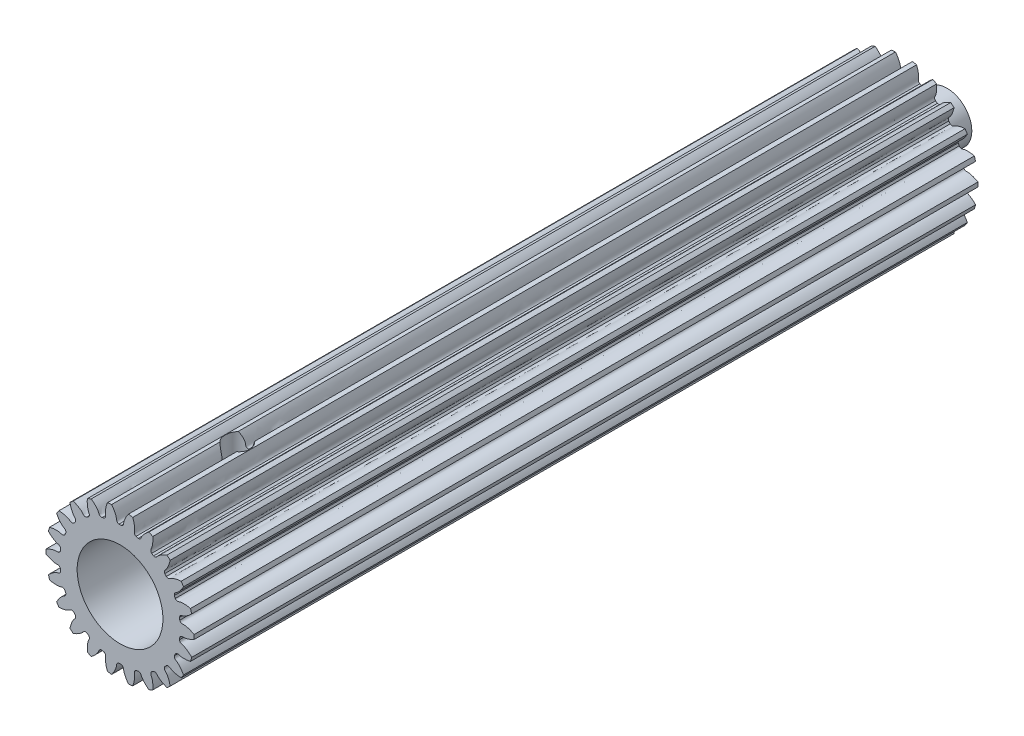
SolidWorks part; units mm, degrees
ref_plane "前视基准面" through (0, 0, 0) normal (0, 0, 1) x (1, 0, 0)
ref_plane "上视基准面" through (0, 0, 0) normal (0, 1, 0) x (1, 0, 0)
ref_plane "右视基准面" through (0, 0, 0) normal (1, 0, 0) x (0, 0, -1)
sketch "草图1" plane through (0, 0, 0) normal (0, 0, 1) x (1, 0, 0)
  circle A0 centre (0, 0) radius 12
extrude "凸台-拉伸1" add sketch "草图1" along normal blind 30
ref_axis "基准轴1" through (0, 0, -1.5) along (0, 0, 1)
sketch "草图2" plane through (0, 0, 0) normal (0, 0, 1) x (1, 0, 0)
  line L0 (0, 0) -> (0, 12) construction
  circle A0 centre (0, 0) radius 12 construction
  arc A1 (0.1857, 9.7482) -> (-0.1857, 9.7482) centre (0, 0) ccw
  arc A2 (3.0856, 13.5599) -> (-3.0856, 13.5599) centre (0, 0) ccw
  spline S0 degree 3 poles (0.1857, 9.7482) (0.5882, 9.8762) (0.5483, 10.1518) (0.5996, 10.4216) (0.606, 10.4519) (0.6139, 10.4862) (0.6235, 10.5243) (0.6349, 10.5661) (0.6484, 10.6117) (0.664, 10.661) (0.6819, 10.7139) (0.7023, 10.7703) (0.7253, 10.8301) (0.7511, 10.8933) (0.7797, 10.9597) (0.8114, 11.0293) (0.8462, 11.1021) (0.8843, 11.1778) (0.9259, 11.2563) (0.9711, 11.3377) (1.0199, 11.4217) (1.0726, 11.5082) (1.1292, 11.5972) (1.1899, 11.6884) (1.2547, 11.7818) (1.3238, 11.8773) (1.3973, 11.9746) (1.4753, 12.0737) (1.5579, 12.1744) (1.6452, 12.2766) (1.7372, 12.3802) (1.8341, 12.4849) (1.9359, 12.5906) (2.0428, 12.6972) (2.1547, 12.8044) (2.2718, 12.9123) (2.3942, 13.0205) (2.5218, 13.1289) (2.6548, 13.2373) (2.8415, 13.3834) (2.9864, 13.49) (3.0856, 13.5599) knots 0 0 0 0 0.157021 0.162531 0.168888 0.176093 0.184146 0.193046 0.202794 0.213389 0.224833 0.237123 0.250262 0.264248 0.279082 0.294763 0.311292 0.328669 0.346893 0.365965 0.385884 0.406652 0.428266 0.450729 0.474039 0.498197 0.523202 0.549055 0.575756 0.603304 0.6317 0.660944 0.691035 0.721974 0.75376 0.786395 0.819876 0.854206 0.889383 0.925408 1 1 1 1
  spline S1 degree 3 poles (-0.1857, 9.7482) (-0.5882, 9.8762) (-0.5483, 10.1518) (-0.5996, 10.4216) (-0.606, 10.4519) (-0.6139, 10.4862) (-0.6235, 10.5243) (-0.6349, 10.5661) (-0.6484, 10.6117) (-0.664, 10.661) (-0.6819, 10.7139) (-0.7023, 10.7703) (-0.7253, 10.8301) (-0.7511, 10.8933) (-0.7797, 10.9597) (-0.8114, 11.0293) (-0.8462, 11.1021) (-0.8843, 11.1778) (-0.9259, 11.2563) (-0.9711, 11.3377) (-1.0199, 11.4217) (-1.0726, 11.5082) (-1.1292, 11.5972) (-1.1899, 11.6884) (-1.2547, 11.7818) (-1.3238, 11.8773) (-1.3973, 11.9746) (-1.4753, 12.0737) (-1.5579, 12.1744) (-1.6452, 12.2766) (-1.7372, 12.3802) (-1.8341, 12.4849) (-1.9359, 12.5906) (-2.0428, 12.6972) (-2.1547, 12.8044) (-2.2718, 12.9123) (-2.3942, 13.0205) (-2.5218, 13.1289) (-2.6548, 13.2373) (-2.8415, 13.3834) (-2.9864, 13.49) (-3.0856, 13.5599) knots 0 0 0 0 0.157021 0.162531 0.168888 0.176093 0.184146 0.193046 0.202794 0.213389 0.224833 0.237123 0.250262 0.264248 0.279082 0.294763 0.311292 0.328669 0.346893 0.365965 0.385884 0.406652 0.428266 0.450729 0.474039 0.498197 0.523202 0.549055 0.575756 0.603304 0.6317 0.660944 0.691035 0.721974 0.75376 0.786395 0.819876 0.854206 0.889383 0.925408 1 1 1 1
extrude "切除-拉伸1" cut sketch "草图2" along normal through all
pattern_circular "阵列(圆周)1" count 22 every 16.364 about axis through (0, 0, -1.5) along (0, 0, 1) of "切除-拉伸1"
sketch "草图3" plane through (0, 0, 0) normal (0, 0, 1) x (1, 0, 0)
  circle A0 centre (0, 0) radius 11 construction
  dimension "Dn" = 22
sketch "草图4" plane through (0, 0, 0) normal (0, 0, -1) x (-1, 0, 0)
  arc A45 (2.9245, 9.3011) -> (2.5682, 9.4057) centre (0, 0) ccw
  arc A46 (2.0557, 11.8226) -> (1.3584, 11.9229) centre (0, 0) ccw
  arc A47 (0.1857, 9.7482) -> (-0.1857, 9.7482) centre (0, 0) ccw
  arc A48 (-1.3584, 11.9229) -> (-2.0557, 11.8226) centre (0, 0) ccw
  arc A49 (-2.5682, 9.4057) -> (-2.9245, 9.3011) centre (0, 0) ccw
  arc A50 (-4.6624, 11.0572) -> (-5.3032, 10.7646) centre (0, 0) ccw
  arc A51 (-5.1141, 8.3011) -> (-5.4265, 8.1004) centre (0, 0) ccw
  arc A52 (-7.5887, 9.2958) -> (-8.1211, 8.8344) centre (0, 0) ccw
  arc A53 (-7.2456, 6.5241) -> (-7.4888, 6.2434) centre (0, 0) ccw
  arc A54 (-9.9003, 6.7812) -> (-10.2811, 6.1886) centre (0, 0) ccw
  arc A55 (-8.7902, 4.2184) -> (-8.9444, 3.8807) centre (0, 0) ccw
  arc A56 (-11.4097, 3.7173) -> (-11.6082, 3.0414) centre (0, 0) ccw
  arc A57 (-9.6226, 1.5711) -> (-9.6754, 1.2035) centre (0, 0) ccw
  arc A58 (-11.9948, 0.3522) -> (-11.9948, -0.3522) centre (0, 0) ccw
  arc A59 (-9.6754, -1.2035) -> (-9.6226, -1.5711) centre (0, 0) ccw
  arc A60 (-11.6082, -3.0414) -> (-11.4097, -3.7173) centre (0, 0) ccw
  arc A61 (-8.9444, -3.8807) -> (-8.7902, -4.2184) centre (0, 0) ccw
  arc A62 (-10.2811, -6.1886) -> (-9.9003, -6.7812) centre (0, 0) ccw
  arc A63 (-7.4888, -6.2434) -> (-7.2456, -6.5241) centre (0, 0) ccw
  arc A64 (-8.1211, -8.8344) -> (-7.5887, -9.2958) centre (0, 0) ccw
  arc A65 (-5.4265, -8.1004) -> (-5.1141, -8.3011) centre (0, 0) ccw
  arc A66 (-5.3032, -10.7646) -> (-4.6624, -11.0572) centre (0, 0) ccw
  arc A67 (-2.9245, -9.3011) -> (-2.5682, -9.4057) centre (0, 0) ccw
  arc A68 (-2.0557, -11.8226) -> (-1.3584, -11.9229) centre (0, 0) ccw
  arc A69 (-0.1857, -9.7482) -> (0.1857, -9.7482) centre (0, 0) ccw
  arc A70 (1.3584, -11.9229) -> (2.0557, -11.8226) centre (0, 0) ccw
  arc A71 (2.5682, -9.4057) -> (2.9245, -9.3011) centre (0, 0) ccw
  arc A72 (4.6624, -11.0572) -> (5.3032, -10.7646) centre (0, 0) ccw
  arc A73 (5.1141, -8.3011) -> (5.4265, -8.1004) centre (0, 0) ccw
  arc A74 (7.5887, -9.2958) -> (8.1211, -8.8344) centre (0, 0) ccw
  arc A75 (7.2456, -6.5241) -> (7.4888, -6.2434) centre (0, 0) ccw
  arc A76 (9.9003, -6.7812) -> (10.2811, -6.1886) centre (0, 0) ccw
  arc A77 (8.7902, -4.2184) -> (8.9444, -3.8807) centre (0, 0) ccw
  arc A78 (11.4097, -3.7173) -> (11.6082, -3.0414) centre (0, 0) ccw
  arc A79 (9.6226, -1.5711) -> (9.6754, -1.2035) centre (0, 0) ccw
  arc A80 (11.9948, -0.3522) -> (11.9948, 0.3522) centre (0, 0) ccw
  arc A81 (9.6754, 1.2035) -> (9.6226, 1.5711) centre (0, 0) ccw
  arc A82 (11.6082, 3.0414) -> (11.4097, 3.7173) centre (0, 0) ccw
  arc A83 (8.9444, 3.8807) -> (8.7902, 4.2184) centre (0, 0) ccw
  arc A84 (10.2811, 6.1886) -> (9.9003, 6.7812) centre (0, 0) ccw
  arc A85 (7.4888, 6.2434) -> (7.2456, 6.5241) centre (0, 0) ccw
  arc A86 (8.1211, 8.8344) -> (7.5887, 9.2958) centre (0, 0) ccw
  arc A87 (5.4265, 8.1004) -> (5.1141, 8.3011) centre (0, 0) ccw
  arc A88 (5.3032, 10.7646) -> (4.6624, 11.0572) centre (0, 0) ccw
  arc A89 (2.9245, 9.3011) -> (2.5682, 9.4057) centre (0, 0) ccw
  arc A90 (2.0557, 11.8226) -> (1.3584, 11.9229) centre (0, 0) ccw
  arc A91 (0.1857, 9.7482) -> (-0.1857, 9.7482) centre (0, 0) ccw
  arc A92 (-1.3584, 11.9229) -> (-2.0557, 11.8226) centre (0, 0) ccw
  arc A93 (-2.5682, 9.4057) -> (-2.9245, 9.3011) centre (0, 0) ccw
  arc A94 (-4.6624, 11.0572) -> (-5.3032, 10.7646) centre (0, 0) ccw
  arc A95 (-5.1141, 8.3011) -> (-5.4265, 8.1004) centre (0, 0) ccw
  arc A96 (-7.5887, 9.2958) -> (-8.1211, 8.8344) centre (0, 0) ccw
  arc A97 (-7.2456, 6.5241) -> (-7.4888, 6.2434) centre (0, 0) ccw
  arc A98 (-9.9003, 6.7812) -> (-10.2811, 6.1886) centre (0, 0) ccw
  arc A99 (-8.7902, 4.2184) -> (-8.9444, 3.8807) centre (0, 0) ccw
  arc A100 (-11.4097, 3.7173) -> (-11.6082, 3.0414) centre (0, 0) ccw
  arc A101 (-9.6226, 1.5711) -> (-9.6754, 1.2035) centre (0, 0) ccw
  arc A102 (-11.9948, 0.3522) -> (-11.9948, -0.3522) centre (0, 0) ccw
  arc A103 (-9.6754, -1.2035) -> (-9.6226, -1.5711) centre (0, 0) ccw
  arc A104 (-11.6082, -3.0414) -> (-11.4097, -3.7173) centre (0, 0) ccw
  arc A105 (-8.9444, -3.8807) -> (-8.7902, -4.2184) centre (0, 0) ccw
  arc A106 (-10.2811, -6.1886) -> (-9.9003, -6.7812) centre (0, 0) ccw
  arc A107 (-7.4888, -6.2434) -> (-7.2456, -6.5241) centre (0, 0) ccw
  arc A108 (-8.1211, -8.8344) -> (-7.5887, -9.2958) centre (0, 0) ccw
  arc A109 (-5.4265, -8.1004) -> (-5.1141, -8.3011) centre (0, 0) ccw
  arc A110 (-5.3032, -10.7646) -> (-4.6624, -11.0572) centre (0, 0) ccw
  arc A111 (-2.9245, -9.3011) -> (-2.5682, -9.4057) centre (0, 0) ccw
  arc A112 (-2.0557, -11.8226) -> (-1.3584, -11.9229) centre (0, 0) ccw
  arc A113 (-0.1857, -9.7482) -> (0.1857, -9.7482) centre (0, 0) ccw
  arc A114 (1.3584, -11.9229) -> (2.0557, -11.8226) centre (0, 0) ccw
  arc A115 (2.5682, -9.4057) -> (2.9245, -9.3011) centre (0, 0) ccw
  arc A116 (4.6624, -11.0572) -> (5.3032, -10.7646) centre (0, 0) ccw
  arc A117 (5.1141, -8.3011) -> (5.4265, -8.1004) centre (0, 0) ccw
  arc A118 (7.5887, -9.2958) -> (8.1211, -8.8344) centre (0, 0) ccw
  arc A119 (7.2456, -6.5241) -> (7.4888, -6.2434) centre (0, 0) ccw
  arc A120 (9.9003, -6.7812) -> (10.2811, -6.1886) centre (0, 0) ccw
  arc A121 (8.7902, -4.2184) -> (8.9444, -3.8807) centre (0, 0) ccw
  arc A122 (11.4097, -3.7173) -> (11.6082, -3.0414) centre (0, 0) ccw
  arc A123 (9.6226, -1.5711) -> (9.6754, -1.2035) centre (0, 0) ccw
  arc A124 (11.9948, -0.3522) -> (11.9948, 0.3522) centre (0, 0) ccw
  arc A125 (9.6754, 1.2035) -> (9.6226, 1.5711) centre (0, 0) ccw
  arc A126 (11.6082, 3.0414) -> (11.4097, 3.7173) centre (0, 0) ccw
  arc A127 (8.9444, 3.8807) -> (8.7902, 4.2184) centre (0, 0) ccw
  arc A128 (10.2811, 6.1886) -> (9.9003, 6.7812) centre (0, 0) ccw
  arc A129 (7.4888, 6.2434) -> (7.2456, 6.5241) centre (0, 0) ccw
  arc A130 (8.1211, 8.8344) -> (7.5887, 9.2958) centre (0, 0) ccw
  arc A131 (5.4265, 8.1004) -> (5.1141, 8.3011) centre (0, 0) ccw
  arc A132 (5.3032, 10.7646) -> (4.6624, 11.0572) centre (0, 0) ccw
  spline S44 degree 3 poles (-4691.9968, 1724.857) (174.4884, -109.8043) (25.1874, 28.642) (4.2738, 10.7434) (4.1283, 10.6084) (3.9999, 10.4794) (3.888, 10.3576) (3.7917, 10.2441) (3.7102, 10.1398) (3.6518, 10.0587) (3.6037, 9.9872) (3.5713, 9.9359) (3.5381, 9.8795) (3.5167, 9.8409) (1.0497, 5.0233) (32.2983, -16.5867) (-4207.9876, 2704.0668) knots -16.292514 -16.292514 -16.292514 -16.292514 0.549271 0.593348 0.634035 0.671331 0.705237 0.735752 0.762877 0.786611 0.797206 0.815854 0.823907 0.837469 0.842979 4.152603 4.152603 4.152603 4.152603 only from (4.6624, 11.0572) to (2.9245, 9.3011)
  spline S45 degree 3 poles (5001.3704, -0.2037) (-36.1358, 3.5083) (1.8328, 4.7936) (2.3619, 10.18) (2.3658, 10.2385) (2.3681, 10.3211) (2.3668, 10.4204) (2.3608, 10.536) (2.3486, 10.6678) (2.329, 10.8154) (2.3007, 10.9784) (2.2624, 11.1562) (2.213, 11.3485) (2.1511, 11.5544) (-7.3751, 39.2152) (-216.6487, -6.4787) (4883.8757, -1066.3578) knots -3.152484 -3.152484 -3.152484 -3.152484 0.157021 0.162531 0.176093 0.193046 0.213389 0.237123 0.264248 0.294763 0.328669 0.365965 0.406652 0.450729 0.498197 18.395757 18.395757 18.395757 18.395757 only from (2.5682, 9.4057) to (2.0557, 11.8226)
  spline S46 degree 3 poles (-4987.8863, 333.1) (198.3558, -56.1974) (16.0978, 34.5779) (1.0739, 11.5123) (0.9723, 11.3417) (0.8855, 11.1818) (0.8124, 11.0334) (0.752, 10.8973) (0.7032, 10.7743) (0.6701, 10.6801) (0.644, 10.5979) (0.6274, 10.5396) (0.6113, 10.4761) (0.6018, 10.4331) (-0.4081, 5.1156) (35.663, -6.8153) (-4799.3582, 1409.006) knots -16.292514 -16.292514 -16.292514 -16.292514 0.549271 0.593348 0.634035 0.671331 0.705237 0.735752 0.762877 0.786611 0.797206 0.815854 0.823907 0.837469 0.842979 4.152603 4.152603 4.152603 4.152603 only from (1.3584, 11.9229) to (0.1857, 9.7482)
  spline S47 degree 3 poles (4798.8372, 1408.8534) (-35.6605, -6.8145) (0.408, 5.1157) (-0.6018, 10.4331) (-0.6145, 10.4903) (-0.6356, 10.5702) (-0.6648, 10.6651) (-0.7032, 10.7743) (-0.752, 10.8973) (-0.8124, 11.0334) (-0.8855, 11.1818) (-0.9723, 11.3417) (-1.0739, 11.5123) (-1.1913, 11.6924) (-18.1245, 35.5489) (-206.0477, -67.2532) (4986.4721, 352.784) knots -3.152484 -3.152484 -3.152484 -3.152484 0.157021 0.162531 0.176093 0.193046 0.213389 0.237123 0.264248 0.294763 0.328669 0.365965 0.406652 0.450729 0.498197 18.395757 18.395757 18.395757 18.395757 only from (-0.1857, 9.7482) to (-1.3584, 11.9229)
  spline S48 degree 3 poles (-4879.687, -1085.6429) (206.1537, 1.9623) (5.704, 37.7126) (-2.213, 11.3485) (-2.2624, 11.1562) (-2.3007, 10.9784) (-2.329, 10.8154) (-2.3486, 10.6678) (-2.3608, 10.536) (-2.366, 10.4362) (-2.3678, 10.3501) (-2.3674, 10.2894) (-2.3649, 10.224) (-2.3619, 10.18) (-1.8328, 4.7934) (36.1385, 3.5082) (-5001.9133, -0.2041) knots -16.292514 -16.292514 -16.292514 -16.292514 0.549271 0.593348 0.634035 0.671331 0.705237 0.735752 0.762877 0.786611 0.797206 0.815854 0.823907 0.837469 0.842979 4.152603 4.152603 4.152603 4.152603 only from (-2.0557, 11.8226) to (-2.5682, 9.4057)
  spline S49 degree 3 poles (4207.5307, 2703.7736) (-32.2961, -16.5852) (-1.0498, 5.0235) (-3.5167, 9.8409) (-3.5451, 9.8922) (-3.5879, 9.963) (-3.6426, 10.0458) (-3.7102, 10.1398) (-3.7917, 10.2441) (-3.888, 10.3576) (-3.9999, 10.4794) (-4.1283, 10.6084) (-4.2738, 10.7434) (-4.4372, 10.8832) (-27.4056, 29.0026) (-178.7539, -122.5793) (4685.0942, 1743.3453) knots -3.152484 -3.152484 -3.152484 -3.152484 0.157021 0.162531 0.176093 0.193046 0.213389 0.237123 0.264248 0.294763 0.328669 0.365965 0.406652 0.450729 0.498197 18.395757 18.395757 18.395757 18.395757 only from (-2.9245, 9.3011) to (-4.6624, 11.0572)
  spline S50 degree 3 poles (-4376.1644, -2416.4334) (197.2501, 59.963) (-5.152, 37.7919) (-5.3206, 10.2653) (-5.3138, 10.0669) (-5.3004, 9.8855) (-5.2817, 9.7211) (-5.2589, 9.574) (-5.2335, 9.4441) (-5.2104, 9.3469) (-5.1879, 9.2637) (-5.1704, 9.2057) (-5.1495, 9.1436) (-5.1343, 9.1022) (-3.109, 4.0829) (33.6863, 13.5475) (-4799.2432, -1409.3977) knots -16.292514 -16.292514 -16.292514 -16.292514 0.549271 0.593348 0.634035 0.671331 0.705237 0.735752 0.762877 0.786611 0.797206 0.815854 0.823907 0.837469 0.842979 4.152603 4.152603 4.152603 4.152603 only from (-5.3032, 10.7646) to (-5.1141, 8.3011)
  spline S51 degree 3 poles (3275.3551, 3779.6502) (-26.3153, -25.0122) (-2.4225, 4.5242) (-6.1468, 8.4515) (-6.1884, 8.4928) (-6.2494, 8.5486) (-6.3253, 8.6126) (-6.4166, 8.6838) (-6.5242, 8.7609) (-6.6486, 8.8427) (-6.7903, 8.928) (-6.9498, 9.0156) (-7.1274, 9.1041) (-7.3236, 9.1923) (-34.4665, 20.1068) (-136.9785, -167.9748) (4004.1579, 2992.6711) knots -3.152484 -3.152484 -3.152484 -3.152484 0.157021 0.162531 0.176093 0.193046 0.213389 0.237123 0.264248 0.294763 0.328669 0.365965 0.406652 0.450729 0.498197 18.395757 18.395757 18.395757 18.395757 only from (-5.4265, 8.1004) to (-7.5887, 9.2958)
  spline S52 degree 3 poles (-3518.1111, -3551.4589) (172.3666, 113.1059) (-15.5905, 34.8096) (-7.9971, 8.3505) (-7.9348, 8.1621) (-7.8708, 7.9917) (-7.8065, 7.8393) (-7.7432, 7.7046) (-7.6822, 7.5871) (-7.6327, 7.5003) (-7.5876, 7.4269) (-7.5545, 7.3761) (-7.517, 7.3224) (-7.4907, 7.287) (-4.1333, 3.0416) (28.505, 22.4892) (-4207.7669, -2704.4102) knots -16.292514 -16.292514 -16.292514 -16.292514 0.549271 0.593348 0.634035 0.671331 0.705237 0.735752 0.762877 0.786611 0.797206 0.815854 0.823907 0.837469 0.842979 4.152603 4.152603 4.152603 4.152603 only from (-8.1211, 8.8344) to (-7.2456, 6.5241)
  spline S53 degree 3 poles (2077.8297, 4549.322) (-18.2026, -31.4129) (-3.599, 3.6585) (-8.2789, 6.3774) (-8.3304, 6.4053) (-8.4047, 6.4416) (-8.4955, 6.4817) (-8.6032, 6.5243) (-8.7281, 6.5679) (-8.8705, 6.6114) (-9.0305, 6.6533) (-9.2082, 6.6924) (-9.4036, 6.7273) (-9.6167, 6.7566) (-38.7351, 9.582) (-84.1059, -199.762) (2998.8285, 3999.5485) knots -3.152484 -3.152484 -3.152484 -3.152484 0.157021 0.162531 0.176093 0.193046 0.213389 0.237123 0.264248 0.294763 0.328669 0.365965 0.406652 0.450729 0.498197 18.395757 18.395757 18.395757 18.395757 only from (-7.4888, 6.2434) to (-9.9003, 6.7812)
  spline S54 degree 3 poles (-2375.0413, -4398.7663) (133.5189, 157.0856) (-24.766, 29.0072) (-10.0258, 5.7592) (-9.9129, 5.596) (-9.8035, 5.4506) (-9.6989, 5.3224) (-9.6002, 5.211) (-9.5086, 5.1155) (-9.4366, 5.0462) (-9.3727, 4.9884) (-9.3266, 4.949) (-9.2755, 4.908) (-9.2403, 4.8814) (-4.8228, 1.7539) (21.0144, 29.6091) (-3275.4024, -3780.3275) knots -16.292514 -16.292514 -16.292514 -16.292514 0.549271 0.593348 0.634035 0.671331 0.705237 0.735752 0.762877 0.786611 0.797206 0.815854 0.823907 0.837469 0.842979 4.152603 4.152603 4.152603 4.152603 only from (-10.2811, 6.1886) to (-8.7902, 4.2184)
  spline S55 degree 3 poles (711.9709, 4950.4347) (-8.6152, -35.2687) (-4.4839, 2.4963) (-9.7402, 3.7867) (-9.7976, 3.7989) (-9.8791, 3.8128) (-9.9775, 3.8257) (-10.0928, 3.8362) (-10.225, 3.8429) (-10.3738, 3.8445) (-10.5392, 3.8396) (-10.7207, 3.8271) (-10.918, 3.8055) (-11.1307, 3.7736) (-39.8656, -1.7191) (-24.4196, -215.3656) (1750.5518, 4682.4063) knots -3.152484 -3.152484 -3.152484 -3.152484 0.157021 0.162531 0.176093 0.193046 0.213389 0.237123 0.264248 0.294763 0.328669 0.365965 0.406652 0.450729 0.498197 18.395757 18.395757 18.395757 18.395757 only from (-8.9444, 3.8807) to (-11.4097, 3.7173)
  spline S56 degree 3 poles (-1039.5597, -4889.7118) (83.8543, 188.3391) (-31.935, 20.8549) (-11.2422, 2.7013) (-11.0879, 2.5765) (-10.942, 2.4678) (-10.8055, 2.3743) (-10.6794, 2.2952) (-10.5646, 2.2294) (-10.476, 2.1832) (-10.3984, 2.1457) (-10.3431, 2.1209) (-10.2825, 2.096) (-10.2412, 2.0804) (-5.1216, 0.3241) (11.8213, 34.3301) (-2077.6842, -4549.9852) knots -16.292514 -16.292514 -16.292514 -16.292514 0.549271 0.593348 0.634035 0.671331 0.705237 0.735752 0.762877 0.786611 0.797206 0.815854 0.823907 0.837469 0.842979 4.152603 4.152603 4.152603 4.152603 only from (-11.6082, 3.0414) to (-9.6226, 1.5711)
  spline S57 degree 3 poles (-711.5676, 4950.4927) (1.6701, -36.2673) (-5.0056, 1.1319) (-10.4125, 0.8891) (-10.4709, 0.8847) (-10.5531, 0.8751) (-10.6512, 0.8598) (-10.7647, 0.8373) (-10.8934, 0.8065) (-11.0367, 0.7661) (-11.194, 0.7149) (-11.3647, 0.6517) (-11.5479, 0.5754) (-11.743, 0.4849) (-37.7664, -12.8809) (37.245, -213.5216) (360.4559, 4985.9234) knots -3.152484 -3.152484 -3.152484 -3.152484 0.157021 0.162531 0.176093 0.193046 0.213389 0.237123 0.264248 0.294763 0.328669 0.365965 0.406652 0.450729 0.498197 18.395757 18.395757 18.395757 18.395757 only from (-9.6754, 1.2035) to (-11.9948, 0.3522)
  spline S58 degree 3 poles (380.1407, -4984.5219) (27.3964, 204.3346) (-36.5169, 11.0129) (-11.5479, -0.5754) (-11.3647, -0.6517) (-11.194, -0.7149) (-11.0367, -0.7661) (-10.8934, -0.8065) (-10.7647, -0.8373) (-10.6667, -0.8567) (-10.5817, -0.8708) (-10.5216, -0.879) (-10.4565, -0.8858) (-10.4125, -0.8891) (-5.0054, -1.1319) (1.6706, 36.27) (-711.6445, -4951.0301) knots -16.292514 -16.292514 -16.292514 -16.292514 0.549271 0.593348 0.634035 0.671331 0.705237 0.735752 0.762877 0.786611 0.797206 0.815854 0.823907 0.837469 0.842979 4.152603 4.152603 4.152603 4.152603 only from (-11.9948, -0.3522) to (-9.6754, -1.2035)
  spline S59 degree 3 poles (-2077.4591, 4549.4912) (11.8201, -34.3277) (-5.1217, -0.3242) (-10.2412, -2.0804) (-10.296, -2.1012) (-10.3722, -2.1335) (-10.4619, -2.1758) (-10.5646, -2.2294) (-10.6794, -2.2952) (-10.8055, -2.3743) (-10.942, -2.4678) (-11.0879, -2.5765) (-11.2422, -2.7014) (-11.4039, -2.8432) (-32.6077, -22.9992) (95.8923, -194.3793) (-1058.8421, 4885.5106) knots -3.152484 -3.152484 -3.152484 -3.152484 0.157021 0.162531 0.176093 0.193046 0.213389 0.237123 0.264248 0.294763 0.328669 0.365965 0.406652 0.450729 0.498197 18.395757 18.395757 18.395757 18.395757 only from (-9.6226, -1.5711) to (-11.6082, -3.0414)
  spline S60 degree 3 poles (1769.0445, -4675.5157) (-31.2811, 203.776) (-38.1404, 0.2788) (-10.918, -3.8055) (-10.7207, -3.8271) (-10.5392, -3.8396) (-10.3738, -3.8445) (-10.225, -3.8429) (-10.0928, -3.8362) (-9.9933, -3.8272) (-9.9078, -3.8167) (-9.8478, -3.8076) (-9.7834, -3.7958) (-9.7402, -3.7867) (-4.4837, -2.4963) (-8.6155, 35.2714) (712.0485, -4950.972) knots -16.292514 -16.292514 -16.292514 -16.292514 0.549271 0.593348 0.634035 0.671331 0.705237 0.735752 0.762877 0.786611 0.797206 0.815854 0.823907 0.837469 0.842979 4.152603 4.152603 4.152603 4.152603 only from (-11.4097, -3.7173) to (-8.9444, -3.8807)
  spline S61 degree 3 poles (-3275.0472, 3779.917) (21.0126, -29.6071) (-4.823, -1.754) (-9.2403, -4.8814) (-9.287, -4.9168) (-9.351, -4.9692) (-9.4251, -5.0352) (-9.5086, -5.1155) (-9.6002, -5.211) (-9.6989, -5.3224) (-9.8035, -5.4506) (-9.9129, -5.596) (-10.0258, -5.7592) (-10.1409, -5.9408) (-24.8072, -31.2542) (146.771, -159.4896) (-2392.359, 4389.3028) knots -3.152484 -3.152484 -3.152484 -3.152484 0.157021 0.162531 0.176093 0.193046 0.213389 0.237123 0.264248 0.294763 0.328669 0.365965 0.406652 0.450729 0.498197 18.395757 18.395757 18.395757 18.395757 only from (-8.7902, -4.2184) to (-10.2811, -6.1886)
  spline S62 degree 3 poles (3014.6307, -3987.7271) (-87.4243, 186.7088) (-36.674, -10.4779) (-9.4036, -6.7273) (-9.2082, -6.6924) (-9.0305, -6.6533) (-8.8705, -6.6114) (-8.7281, -6.5679) (-8.6032, -6.5243) (-8.5102, -6.4876) (-8.4311, -6.4535) (-8.3761, -6.4279) (-8.3177, -6.3984) (-8.2789, -6.3774) (-3.5988, -3.6584) (-18.2036, 31.4154) (2078.0555, -4549.8156) knots -16.292514 -16.292514 -16.292514 -16.292514 0.549271 0.593348 0.634035 0.671331 0.705237 0.735752 0.762877 0.786611 0.797206 0.815854 0.823907 0.837469 0.842979 4.152603 4.152603 4.152603 4.152603 only from (-9.9003, -6.7812) to (-7.4888, -6.2434)
  spline S63 degree 3 poles (-4207.3104, 2704.1164) (28.5027, -22.4878) (-4.1334, -3.0417) (-7.4907, -7.287) (-7.5256, -7.3341) (-7.5722, -7.4024) (-7.6248, -7.4866) (-7.6822, -7.5871) (-7.7432, -7.7046) (-7.8065, -7.8393) (-7.8708, -7.9917) (-7.9348, -8.1621) (-7.9971, -8.3505) (-8.0564, -8.5572) (-14.997, -36.9772) (185.7591, -111.679) (-3532.0611, 3537.4998) knots -3.152484 -3.152484 -3.152484 -3.152484 0.157021 0.162531 0.176093 0.193046 0.213389 0.237123 0.264248 0.294763 0.328669 0.365965 0.406652 0.450729 0.498197 18.395757 18.395757 18.395757 18.395757 only from (-7.2456, -6.5241) to (-8.1211, -8.8344)
  spline S64 degree 3 poles (4015.9895, -2976.8765) (-136.485, 154.5155) (-32.2365, -20.3857) (-7.1274, -9.1041) (-6.9498, -9.0156) (-6.7903, -8.928) (-6.6486, -8.8427) (-6.5242, -8.7609) (-6.4166, -8.6838) (-6.3378, -8.6224) (-6.2715, -8.5674) (-6.2259, -8.5273) (-6.1781, -8.4826) (-6.1468, -8.4515) (-2.4224, -4.5241) (-26.317, 25.0143) (3275.7109, -3780.0602) knots -16.292514 -16.292514 -16.292514 -16.292514 0.549271 0.593348 0.634035 0.671331 0.705237 0.735752 0.762877 0.786611 0.797206 0.815854 0.823907 0.837469 0.842979 4.152603 4.152603 4.152603 4.152603 only from (-7.5887, -9.2958) to (-5.4265, -8.1004)
  spline S65 degree 3 poles (-4798.7224, 1409.2443) (33.6837, -13.5468) (-3.109, -4.083) (-5.1343, -9.1022) (-5.1545, -9.1572) (-5.18, -9.2359) (-5.2067, -9.3315) (-5.2335, -9.4441) (-5.2589, -9.574) (-5.2817, -9.7211) (-5.3004, -9.8855) (-5.3138, -10.0669) (-5.3206, -10.2653) (-5.3192, -10.4804) (-3.9719, -39.7045) (209.6982, -54.8208) (-4385.6167, 2399.1096) knots -3.152484 -3.152484 -3.152484 -3.152484 0.157021 0.162531 0.176093 0.193046 0.213389 0.237123 0.264248 0.294763 0.328669 0.365965 0.406652 0.450729 0.498197 18.395757 18.395757 18.395757 18.395757 only from (-5.1141, -8.3011) to (-5.3032, -10.7646)
  spline S66 degree 3 poles (4691.9968, -1724.857) (-174.4884, 109.8043) (-25.1874, -28.642) (-4.2738, -10.7434) (-4.1283, -10.6084) (-3.9999, -10.4794) (-3.888, -10.3576) (-3.7917, -10.2441) (-3.7102, -10.1398) (-3.6518, -10.0587) (-3.6037, -9.9872) (-3.5713, -9.9359) (-3.5381, -9.8795) (-3.5167, -9.8409) (-1.0497, -5.0233) (-32.2983, 16.5867) (4207.9876, -2704.0668) knots -16.292514 -16.292514 -16.292514 -16.292514 0.549271 0.593348 0.634035 0.671331 0.705237 0.735752 0.762877 0.786611 0.797206 0.815854 0.823907 0.837469 0.842979 4.152603 4.152603 4.152603 4.152603 only from (-4.6624, -11.0572) to (-2.9245, -9.3011)
  spline S67 degree 3 poles (-5001.3704, 0.2037) (36.1358, -3.5083) (-1.8328, -4.7936) (-2.3619, -10.18) (-2.3658, -10.2385) (-2.3681, -10.3211) (-2.3668, -10.4204) (-2.3608, -10.536) (-2.3486, -10.6678) (-2.329, -10.8154) (-2.3007, -10.9784) (-2.2624, -11.1562) (-2.213, -11.3485) (-2.1511, -11.5544) (7.3751, -39.2152) (216.6487, 6.4787) (-4883.8757, 1066.3578) knots -3.152484 -3.152484 -3.152484 -3.152484 0.157021 0.162531 0.176093 0.193046 0.213389 0.237123 0.264248 0.294763 0.328669 0.365965 0.406652 0.450729 0.498197 18.395757 18.395757 18.395757 18.395757 only from (-2.5682, -9.4057) to (-2.0557, -11.8226)
  spline S68 degree 3 poles (4987.8863, -333.1) (-198.3558, 56.1974) (-16.0978, -34.5779) (-1.0739, -11.5123) (-0.9723, -11.3417) (-0.8855, -11.1818) (-0.8124, -11.0334) (-0.752, -10.8973) (-0.7032, -10.7743) (-0.6701, -10.6801) (-0.644, -10.5979) (-0.6274, -10.5396) (-0.6113, -10.4761) (-0.6018, -10.4331) (0.4081, -5.1156) (-35.663, 6.8153) (4799.3582, -1409.006) knots -16.292514 -16.292514 -16.292514 -16.292514 0.549271 0.593348 0.634035 0.671331 0.705237 0.735752 0.762877 0.786611 0.797206 0.815854 0.823907 0.837469 0.842979 4.152603 4.152603 4.152603 4.152603 only from (-1.3584, -11.9229) to (-0.1857, -9.7482)
  spline S69 degree 3 poles (-4798.8372, -1408.8534) (35.6605, 6.8145) (-0.408, -5.1157) (0.6018, -10.4331) (0.6145, -10.4903) (0.6356, -10.5702) (0.6648, -10.6651) (0.7032, -10.7743) (0.752, -10.8973) (0.8124, -11.0334) (0.8855, -11.1818) (0.9723, -11.3417) (1.0739, -11.5123) (1.1913, -11.6924) (18.1245, -35.5489) (206.0477, 67.2532) (-4986.4721, -352.784) knots -3.152484 -3.152484 -3.152484 -3.152484 0.157021 0.162531 0.176093 0.193046 0.213389 0.237123 0.264248 0.294763 0.328669 0.365965 0.406652 0.450729 0.498197 18.395757 18.395757 18.395757 18.395757 only from (0.1857, -9.7482) to (1.3584, -11.9229)
  spline S70 degree 3 poles (4879.687, 1085.6429) (-206.1537, -1.9623) (-5.704, -37.7126) (2.213, -11.3485) (2.2624, -11.1562) (2.3007, -10.9784) (2.329, -10.8154) (2.3486, -10.6678) (2.3608, -10.536) (2.366, -10.4362) (2.3678, -10.3501) (2.3674, -10.2894) (2.3649, -10.224) (2.3619, -10.18) (1.8328, -4.7934) (-36.1385, -3.5082) (5001.9133, 0.2041) knots -16.292514 -16.292514 -16.292514 -16.292514 0.549271 0.593348 0.634035 0.671331 0.705237 0.735752 0.762877 0.786611 0.797206 0.815854 0.823907 0.837469 0.842979 4.152603 4.152603 4.152603 4.152603 only from (2.0557, -11.8226) to (2.5682, -9.4057)
  spline S71 degree 3 poles (-4207.5307, -2703.7736) (32.2961, 16.5852) (1.0498, -5.0235) (3.5167, -9.8409) (3.5451, -9.8922) (3.5879, -9.963) (3.6426, -10.0458) (3.7102, -10.1398) (3.7917, -10.2441) (3.888, -10.3576) (3.9999, -10.4794) (4.1283, -10.6084) (4.2738, -10.7434) (4.4372, -10.8832) (27.4056, -29.0026) (178.7539, 122.5793) (-4685.0942, -1743.3453) knots -3.152484 -3.152484 -3.152484 -3.152484 0.157021 0.162531 0.176093 0.193046 0.213389 0.237123 0.264248 0.294763 0.328669 0.365965 0.406652 0.450729 0.498197 18.395757 18.395757 18.395757 18.395757 only from (2.9245, -9.3011) to (4.6624, -11.0572)
  spline S72 degree 3 poles (4376.1644, 2416.4334) (-197.2501, -59.963) (5.152, -37.7919) (5.3206, -10.2653) (5.3138, -10.0669) (5.3004, -9.8855) (5.2817, -9.7211) (5.2589, -9.574) (5.2335, -9.4441) (5.2104, -9.3469) (5.1879, -9.2637) (5.1704, -9.2057) (5.1495, -9.1436) (5.1343, -9.1022) (3.109, -4.0829) (-33.6863, -13.5475) (4799.2432, 1409.3977) knots -16.292514 -16.292514 -16.292514 -16.292514 0.549271 0.593348 0.634035 0.671331 0.705237 0.735752 0.762877 0.786611 0.797206 0.815854 0.823907 0.837469 0.842979 4.152603 4.152603 4.152603 4.152603 only from (5.3032, -10.7646) to (5.1141, -8.3011)
  spline S73 degree 3 poles (-3275.3551, -3779.6502) (26.3153, 25.0122) (2.4225, -4.5242) (6.1468, -8.4515) (6.1884, -8.4928) (6.2494, -8.5486) (6.3253, -8.6126) (6.4166, -8.6838) (6.5242, -8.7609) (6.6486, -8.8427) (6.7903, -8.928) (6.9498, -9.0156) (7.1274, -9.1041) (7.3236, -9.1923) (34.4665, -20.1068) (136.9785, 167.9748) (-4004.1579, -2992.6711) knots -3.152484 -3.152484 -3.152484 -3.152484 0.157021 0.162531 0.176093 0.193046 0.213389 0.237123 0.264248 0.294763 0.328669 0.365965 0.406652 0.450729 0.498197 18.395757 18.395757 18.395757 18.395757 only from (5.4265, -8.1004) to (7.5887, -9.2958)
  spline S74 degree 3 poles (3518.1111, 3551.4589) (-172.3666, -113.1059) (15.5905, -34.8096) (7.9971, -8.3505) (7.9348, -8.1621) (7.8708, -7.9917) (7.8065, -7.8393) (7.7432, -7.7046) (7.6822, -7.5871) (7.6327, -7.5003) (7.5876, -7.4269) (7.5545, -7.3761) (7.517, -7.3224) (7.4907, -7.287) (4.1333, -3.0416) (-28.505, -22.4892) (4207.7669, 2704.4102) knots -16.292514 -16.292514 -16.292514 -16.292514 0.549271 0.593348 0.634035 0.671331 0.705237 0.735752 0.762877 0.786611 0.797206 0.815854 0.823907 0.837469 0.842979 4.152603 4.152603 4.152603 4.152603 only from (8.1211, -8.8344) to (7.2456, -6.5241)
  spline S75 degree 3 poles (-2077.8297, -4549.322) (18.2026, 31.4129) (3.599, -3.6585) (8.2789, -6.3774) (8.3304, -6.4053) (8.4047, -6.4416) (8.4955, -6.4817) (8.6032, -6.5243) (8.7281, -6.5679) (8.8705, -6.6114) (9.0305, -6.6533) (9.2082, -6.6924) (9.4036, -6.7273) (9.6167, -6.7566) (38.7351, -9.582) (84.1059, 199.762) (-2998.8285, -3999.5485) knots -3.152484 -3.152484 -3.152484 -3.152484 0.157021 0.162531 0.176093 0.193046 0.213389 0.237123 0.264248 0.294763 0.328669 0.365965 0.406652 0.450729 0.498197 18.395757 18.395757 18.395757 18.395757 only from (7.4888, -6.2434) to (9.9003, -6.7812)
  spline S76 degree 3 poles (2375.0413, 4398.7663) (-133.5189, -157.0856) (24.766, -29.0072) (10.0258, -5.7592) (9.9129, -5.596) (9.8035, -5.4506) (9.6989, -5.3224) (9.6002, -5.211) (9.5086, -5.1155) (9.4366, -5.0462) (9.3727, -4.9884) (9.3266, -4.949) (9.2755, -4.908) (9.2403, -4.8814) (4.8228, -1.7539) (-21.0144, -29.6091) (3275.4024, 3780.3275) knots -16.292514 -16.292514 -16.292514 -16.292514 0.549271 0.593348 0.634035 0.671331 0.705237 0.735752 0.762877 0.786611 0.797206 0.815854 0.823907 0.837469 0.842979 4.152603 4.152603 4.152603 4.152603 only from (10.2811, -6.1886) to (8.7902, -4.2184)
  spline S77 degree 3 poles (-711.9709, -4950.4347) (8.6152, 35.2687) (4.4839, -2.4963) (9.7402, -3.7867) (9.7976, -3.7989) (9.8791, -3.8128) (9.9775, -3.8257) (10.0928, -3.8362) (10.225, -3.8429) (10.3738, -3.8445) (10.5392, -3.8396) (10.7207, -3.8271) (10.918, -3.8055) (11.1307, -3.7736) (39.8656, 1.7191) (24.4196, 215.3656) (-1750.5518, -4682.4063) knots -3.152484 -3.152484 -3.152484 -3.152484 0.157021 0.162531 0.176093 0.193046 0.213389 0.237123 0.264248 0.294763 0.328669 0.365965 0.406652 0.450729 0.498197 18.395757 18.395757 18.395757 18.395757 only from (8.9444, -3.8807) to (11.4097, -3.7173)
  spline S78 degree 3 poles (1039.5597, 4889.7118) (-83.8543, -188.3391) (31.935, -20.8549) (11.2422, -2.7013) (11.0879, -2.5765) (10.942, -2.4678) (10.8055, -2.3743) (10.6794, -2.2952) (10.5646, -2.2294) (10.476, -2.1832) (10.3984, -2.1457) (10.3431, -2.1209) (10.2825, -2.096) (10.2412, -2.0804) (5.1216, -0.3241) (-11.8213, -34.3301) (2077.6842, 4549.9852) knots -16.292514 -16.292514 -16.292514 -16.292514 0.549271 0.593348 0.634035 0.671331 0.705237 0.735752 0.762877 0.786611 0.797206 0.815854 0.823907 0.837469 0.842979 4.152603 4.152603 4.152603 4.152603 only from (11.6082, -3.0414) to (9.6226, -1.5711)
  spline S79 degree 3 poles (711.5676, -4950.4927) (-1.6701, 36.2673) (5.0056, -1.1319) (10.4125, -0.8891) (10.4709, -0.8847) (10.5531, -0.8751) (10.6512, -0.8598) (10.7647, -0.8373) (10.8934, -0.8065) (11.0367, -0.7661) (11.194, -0.7149) (11.3647, -0.6517) (11.5479, -0.5754) (11.743, -0.4849) (37.7664, 12.8809) (-37.245, 213.5216) (-360.4558, -4985.9234) knots -3.152484 -3.152484 -3.152484 -3.152484 0.157021 0.162531 0.176093 0.193046 0.213389 0.237123 0.264248 0.294763 0.328669 0.365965 0.406652 0.450729 0.498197 18.395757 18.395757 18.395757 18.395757 only from (9.6754, -1.2035) to (11.9948, -0.3522)
  spline S80 degree 3 poles (-380.1407, 4984.5219) (-27.3964, -204.3346) (36.5169, -11.0129) (11.5479, 0.5754) (11.3647, 0.6517) (11.194, 0.7149) (11.0367, 0.7661) (10.8934, 0.8065) (10.7647, 0.8373) (10.6667, 0.8567) (10.5817, 0.8708) (10.5216, 0.879) (10.4565, 0.8858) (10.4125, 0.8891) (5.0054, 1.1319) (-1.6706, -36.27) (711.6445, 4951.0301) knots -16.292514 -16.292514 -16.292514 -16.292514 0.549271 0.593348 0.634035 0.671331 0.705237 0.735752 0.762877 0.786611 0.797206 0.815854 0.823907 0.837469 0.842979 4.152603 4.152603 4.152603 4.152603 only from (11.9948, 0.3522) to (9.6754, 1.2035)
  spline S81 degree 3 poles (2077.4591, -4549.4912) (-11.8201, 34.3277) (5.1217, 0.3242) (10.2412, 2.0804) (10.296, 2.1012) (10.3722, 2.1335) (10.4619, 2.1758) (10.5646, 2.2294) (10.6794, 2.2952) (10.8055, 2.3743) (10.942, 2.4678) (11.0879, 2.5765) (11.2422, 2.7014) (11.4039, 2.8432) (32.6077, 22.9992) (-95.8923, 194.3793) (1058.8421, -4885.5106) knots -3.152484 -3.152484 -3.152484 -3.152484 0.157021 0.162531 0.176093 0.193046 0.213389 0.237123 0.264248 0.294763 0.328669 0.365965 0.406652 0.450729 0.498197 18.395757 18.395757 18.395757 18.395757 only from (9.6226, 1.5711) to (11.6082, 3.0414)
  spline S82 degree 3 poles (-1769.0445, 4675.5157) (31.2811, -203.776) (38.1404, -0.2788) (10.918, 3.8055) (10.7207, 3.8271) (10.5392, 3.8396) (10.3738, 3.8445) (10.225, 3.8429) (10.0928, 3.8362) (9.9933, 3.8272) (9.9078, 3.8167) (9.8478, 3.8076) (9.7834, 3.7958) (9.7402, 3.7867) (4.4837, 2.4963) (8.6155, -35.2714) (-712.0485, 4950.972) knots -16.292514 -16.292514 -16.292514 -16.292514 0.549271 0.593348 0.634035 0.671331 0.705237 0.735752 0.762877 0.786611 0.797206 0.815854 0.823907 0.837469 0.842979 4.152603 4.152603 4.152603 4.152603 only from (11.4097, 3.7173) to (8.9444, 3.8807)
  spline S83 degree 3 poles (3275.0472, -3779.917) (-21.0126, 29.6071) (4.823, 1.754) (9.2403, 4.8814) (9.287, 4.9168) (9.351, 4.9692) (9.4251, 5.0352) (9.5086, 5.1155) (9.6002, 5.211) (9.6989, 5.3224) (9.8035, 5.4506) (9.9129, 5.596) (10.0258, 5.7592) (10.1409, 5.9408) (24.8072, 31.2542) (-146.771, 159.4896) (2392.3589, -4389.3028) knots -3.152484 -3.152484 -3.152484 -3.152484 0.157021 0.162531 0.176093 0.193046 0.213389 0.237123 0.264248 0.294763 0.328669 0.365965 0.406652 0.450729 0.498197 18.395757 18.395757 18.395757 18.395757 only from (8.7902, 4.2184) to (10.2811, 6.1886)
  spline S84 degree 3 poles (-3014.6307, 3987.7271) (87.4243, -186.7088) (36.674, 10.4779) (9.4036, 6.7273) (9.2082, 6.6924) (9.0305, 6.6533) (8.8705, 6.6114) (8.7281, 6.5679) (8.6032, 6.5243) (8.5102, 6.4876) (8.4311, 6.4535) (8.3761, 6.4279) (8.3177, 6.3984) (8.2789, 6.3774) (3.5988, 3.6584) (18.2036, -31.4154) (-2078.0555, 4549.8156) knots -16.292514 -16.292514 -16.292514 -16.292514 0.549271 0.593348 0.634035 0.671331 0.705237 0.735752 0.762877 0.786611 0.797206 0.815854 0.823907 0.837469 0.842979 4.152603 4.152603 4.152603 4.152603 only from (9.9003, 6.7812) to (7.4888, 6.2434)
  spline S85 degree 3 poles (4207.3104, -2704.1164) (-28.5027, 22.4878) (4.1334, 3.0417) (7.4907, 7.287) (7.5256, 7.3341) (7.5722, 7.4024) (7.6248, 7.4866) (7.6822, 7.5871) (7.7432, 7.7046) (7.8065, 7.8393) (7.8708, 7.9917) (7.9348, 8.1621) (7.9971, 8.3505) (8.0564, 8.5572) (14.997, 36.9772) (-185.7591, 111.679) (3532.0611, -3537.4998) knots -3.152484 -3.152484 -3.152484 -3.152484 0.157021 0.162531 0.176093 0.193046 0.213389 0.237123 0.264248 0.294763 0.328669 0.365965 0.406652 0.450729 0.498197 18.395757 18.395757 18.395757 18.395757 only from (7.2456, 6.5241) to (8.1211, 8.8344)
  spline S86 degree 3 poles (-4015.9895, 2976.8765) (136.485, -154.5155) (32.2365, 20.3857) (7.1274, 9.1041) (6.9498, 9.0156) (6.7903, 8.928) (6.6486, 8.8427) (6.5242, 8.7609) (6.4166, 8.6838) (6.3378, 8.6224) (6.2715, 8.5674) (6.2259, 8.5273) (6.1781, 8.4826) (6.1468, 8.4515) (2.4224, 4.5241) (26.317, -25.0143) (-3275.7109, 3780.0602) knots -16.292514 -16.292514 -16.292514 -16.292514 0.549271 0.593348 0.634035 0.671331 0.705237 0.735752 0.762877 0.786611 0.797206 0.815854 0.823907 0.837469 0.842979 4.152603 4.152603 4.152603 4.152603 only from (7.5887, 9.2958) to (5.4265, 8.1004)
  spline S87 degree 3 poles (4798.7224, -1409.2443) (-33.6837, 13.5468) (3.109, 4.083) (5.1343, 9.1022) (5.1545, 9.1572) (5.18, 9.2359) (5.2067, 9.3315) (5.2335, 9.4441) (5.2589, 9.574) (5.2817, 9.7211) (5.3004, 9.8855) (5.3138, 10.0669) (5.3206, 10.2653) (5.3192, 10.4804) (3.9719, 39.7045) (-209.6982, 54.8208) (4385.6167, -2399.1096) knots -3.152484 -3.152484 -3.152484 -3.152484 0.157021 0.162531 0.176093 0.193046 0.213389 0.237123 0.264248 0.294763 0.328669 0.365965 0.406652 0.450729 0.498197 18.395757 18.395757 18.395757 18.395757 only from (5.1141, 8.3011) to (5.3032, 10.7646)
  spline S88 degree 3 poles (4.6624, 11.0572) (4.5848, 10.9995) (4.452, 10.8959) (4.2738, 10.7434) (4.1283, 10.6084) (3.9999, 10.4794) (3.888, 10.3576) (3.7917, 10.2441) (3.7102, 10.1398) (3.6518, 10.0587) (3.6037, 9.9872) (3.5713, 9.9359) (3.5381, 9.8795) (3.5167, 9.8409) (3.3862, 9.5861) (3.3468, 9.3104) (2.9245, 9.3011) knots 0.48979 0.48979 0.48979 0.48979 0.549271 0.593348 0.634035 0.671331 0.705237 0.735752 0.762877 0.786611 0.797206 0.815854 0.823907 0.837469 0.842979 1 1 1 1
  spline S89 degree 3 poles (2.5682, 9.4057) (2.2181, 9.6418) (2.334, 9.895) (2.3619, 10.18) (2.3658, 10.2385) (2.3681, 10.3211) (2.3668, 10.4204) (2.3608, 10.536) (2.3486, 10.6678) (2.329, 10.8154) (2.3007, 10.9784) (2.2624, 11.1562) (2.213, 11.3485) (2.1511, 11.5544) (2.0963, 11.7137) (2.0626, 11.8043) (2.0557, 11.8226) knots 0 0 0 0 0.157021 0.162531 0.176093 0.193046 0.213389 0.237123 0.264248 0.294763 0.328669 0.365965 0.406652 0.450729 0.498197 0.51021 0.51021 0.51021 0.51021
  spline S90 degree 3 poles (1.3584, 11.9229) (1.3002, 11.8457) (1.2019, 11.7088) (1.0739, 11.5123) (0.9723, 11.3417) (0.8855, 11.1818) (0.8124, 11.0334) (0.752, 10.8973) (0.7032, 10.7743) (0.6701, 10.6801) (0.644, 10.5979) (0.6274, 10.5396) (0.6113, 10.4761) (0.6018, 10.4331) (0.5483, 10.1518) (0.5882, 9.8762) (0.1857, 9.7482) knots 0.48979 0.48979 0.48979 0.48979 0.549271 0.593348 0.634035 0.671331 0.705237 0.735752 0.762877 0.786611 0.797206 0.815854 0.823907 0.837469 0.842979 1 1 1 1
  spline S91 degree 3 poles (-0.1857, 9.7482) (-0.5882, 9.8762) (-0.5483, 10.1518) (-0.6018, 10.4331) (-0.6145, 10.4903) (-0.6356, 10.5702) (-0.6648, 10.6651) (-0.7032, 10.7743) (-0.752, 10.8973) (-0.8124, 11.0334) (-0.8855, 11.1818) (-0.9723, 11.3417) (-1.0739, 11.5123) (-1.1913, 11.6924) (-1.2888, 11.8298) (-1.3466, 11.9073) (-1.3584, 11.9229) knots 0 0 0 0 0.157021 0.162531 0.176093 0.193046 0.213389 0.237123 0.264248 0.294763 0.328669 0.365965 0.406652 0.450729 0.498197 0.51021 0.51021 0.51021 0.51021
  spline S92 degree 3 poles (-2.0557, 11.8226) (-2.0898, 11.7321) (-2.1455, 11.5732) (-2.213, 11.3485) (-2.2624, 11.1562) (-2.3007, 10.9784) (-2.329, 10.8154) (-2.3486, 10.6678) (-2.3608, 10.536) (-2.366, 10.4362) (-2.3678, 10.3501) (-2.3674, 10.2894) (-2.3649, 10.224) (-2.3619, 10.18) (-2.334, 9.895) (-2.2181, 9.6418) (-2.5682, 9.4057) knots 0.48979 0.48979 0.48979 0.48979 0.549271 0.593348 0.634035 0.671331 0.705237 0.735752 0.762877 0.786611 0.797206 0.815854 0.823907 0.837469 0.842979 1 1 1 1
  spline S93 degree 3 poles (-2.9245, 9.3011) (-3.3468, 9.3104) (-3.3862, 9.5861) (-3.5167, 9.8409) (-3.5451, 9.8922) (-3.5879, 9.963) (-3.6426, 10.0458) (-3.7102, 10.1398) (-3.7917, 10.2441) (-3.888, 10.3576) (-3.9999, 10.4794) (-4.1283, 10.6084) (-4.2738, 10.7434) (-4.4372, 10.8832) (-4.5694, 10.9875) (-4.6468, 11.0456) (-4.6624, 11.0572) knots 0 0 0 0 0.157021 0.162531 0.176093 0.193046 0.213389 0.237123 0.264248 0.294763 0.328669 0.365965 0.406652 0.450729 0.498197 0.51021 0.51021 0.51021 0.51021
  spline S94 degree 3 poles (-5.3032, 10.7646) (-5.3105, 10.6681) (-5.3191, 10.4999) (-5.3206, 10.2653) (-5.3138, 10.0669) (-5.3004, 9.8855) (-5.2817, 9.7211) (-5.2589, 9.574) (-5.2335, 9.4441) (-5.2104, 9.3469) (-5.1879, 9.2637) (-5.1704, 9.2057) (-5.1495, 9.1436) (-5.1343, 9.1022) (-5.0272, 8.8367) (-4.8447, 8.6264) (-5.1141, 8.3011) knots 0.48979 0.48979 0.48979 0.48979 0.549271 0.593348 0.634035 0.671331 0.705237 0.735752 0.762877 0.786611 0.797206 0.815854 0.823907 0.837469 0.842979 1 1 1 1
  spline S95 degree 3 poles (-5.4265, 8.1004) (-5.8343, 7.9904) (-5.9498, 8.2438) (-6.1468, 8.4515) (-6.1884, 8.4928) (-6.2494, 8.5486) (-6.3253, 8.6126) (-6.4166, 8.6838) (-6.5242, 8.7609) (-6.6486, 8.8427) (-6.7903, 8.928) (-6.9498, 9.0156) (-7.1274, 9.1041) (-7.3236, 9.1923) (-7.4798, 9.2551) (-7.5704, 9.289) (-7.5887, 9.2958) knots 0 0 0 0 0.157021 0.162531 0.176093 0.193046 0.213389 0.237123 0.264248 0.294763 0.328669 0.365965 0.406652 0.450729 0.498197 0.51021 0.51021 0.51021 0.51021
  spline S96 degree 3 poles (-8.1211, 8.8344) (-8.1009, 8.7398) (-8.0618, 8.576) (-7.9971, 8.3505) (-7.9348, 8.1621) (-7.8708, 7.9917) (-7.8065, 7.8393) (-7.7432, 7.7046) (-7.6822, 7.5871) (-7.6327, 7.5003) (-7.5876, 7.4269) (-7.5545, 7.3761) (-7.517, 7.3224) (-7.4907, 7.287) (-7.3131, 7.0624) (-7.0788, 6.912) (-7.2456, 6.5241) knots 0.48979 0.48979 0.48979 0.48979 0.549271 0.593348 0.634035 0.671331 0.705237 0.735752 0.762877 0.786611 0.797206 0.815854 0.823907 0.837469 0.842979 1 1 1 1
  spline S97 degree 3 poles (-7.4888, 6.2434) (-7.8491, 6.023) (-8.0313, 6.2336) (-8.2789, 6.3774) (-8.3304, 6.4053) (-8.4047, 6.4416) (-8.4955, 6.4817) (-8.6032, 6.5243) (-8.7281, 6.5679) (-8.8705, 6.6114) (-9.0305, 6.6533) (-9.2082, 6.6924) (-9.4036, 6.7273) (-9.6167, 6.7566) (-9.7843, 6.7729) (-9.8808, 6.7799) (-9.9003, 6.7812) knots 0 0 0 0 0.157021 0.162531 0.176093 0.193046 0.213389 0.237123 0.264248 0.294763 0.328669 0.365965 0.406652 0.450729 0.498197 0.51021 0.51021 0.51021 0.51021
  spline S98 degree 3 poles (-10.2811, 6.1886) (-10.2351, 6.1035) (-10.1514, 5.9573) (-10.0258, 5.7592) (-9.9129, 5.596) (-9.8035, 5.4506) (-9.6989, 5.3224) (-9.6002, 5.211) (-9.5086, 5.1155) (-9.4366, 5.0462) (-9.3727, 4.9884) (-9.3266, 4.949) (-9.2755, 4.908) (-9.2403, 4.8814) (-9.0066, 4.716) (-8.7394, 4.6377) (-8.7902, 4.2184) knots 0.48979 0.48979 0.48979 0.48979 0.549271 0.593348 0.634035 0.671331 0.705237 0.735752 0.762877 0.786611 0.797206 0.815854 0.823907 0.837469 0.842979 1 1 1 1
  spline S99 degree 3 poles (-8.9444, 3.8807) (-9.228, 3.5677) (-9.4622, 3.7184) (-9.7402, 3.7867) (-9.7976, 3.7989) (-9.8791, 3.8128) (-9.9775, 3.8257) (-10.0928, 3.8362) (-10.225, 3.8429) (-10.3738, 3.8445) (-10.5392, 3.8396) (-10.7207, 3.8271) (-10.918, 3.8055) (-11.1307, 3.7736) (-11.2961, 3.742) (-11.3906, 3.7215) (-11.4097, 3.7173) knots 0 0 0 0 0.157021 0.162531 0.176093 0.193046 0.213389 0.237123 0.264248 0.294763 0.328669 0.365965 0.406652 0.450729 0.498197 0.51021 0.51021 0.51021 0.51021
  spline S100 degree 3 poles (-11.6082, 3.0414) (-11.5401, 2.9727) (-11.4186, 2.8561) (-11.2422, 2.7013) (-11.0879, 2.5765) (-10.942, 2.4678) (-10.8055, 2.3743) (-10.6794, 2.2952) (-10.5646, 2.2294) (-10.476, 2.1832) (-10.3984, 2.1457) (-10.3431, 2.1209) (-10.2825, 2.096) (-10.2412, 2.0804) (-9.9704, 1.9875) (-9.692, 1.9877) (-9.6226, 1.5711) knots 0.48979 0.48979 0.48979 0.48979 0.549271 0.593348 0.634035 0.671331 0.705237 0.735752 0.762877 0.786611 0.797206 0.815854 0.823907 0.837469 0.842979 1 1 1 1
  spline S101 degree 3 poles (-9.6754, 1.2035) (-9.8594, 0.8234) (-10.1265, 0.902) (-10.4125, 0.8891) (-10.4709, 0.8847) (-10.5531, 0.8751) (-10.6512, 0.8598) (-10.7647, 0.8373) (-10.8934, 0.8065) (-11.0367, 0.7661) (-11.194, 0.7149) (-11.3647, 0.6517) (-11.5479, 0.5754) (-11.743, 0.4849) (-11.8928, 0.4079) (-11.9777, 0.3617) (-11.9948, 0.3522) knots 0 0 0 0 0.157021 0.162531 0.176093 0.193046 0.213389 0.237123 0.264248 0.294763 0.328669 0.365965 0.406652 0.450729 0.498197 0.51021 0.51021 0.51021 0.51021
  spline S102 degree 3 poles (-11.9948, -0.3522) (-11.9101, -0.3989) (-11.7607, -0.4766) (-11.5479, -0.5754) (-11.3647, -0.6517) (-11.194, -0.7149) (-11.0367, -0.7661) (-10.8934, -0.8065) (-10.7647, -0.8373) (-10.6667, -0.8567) (-10.5817, -0.8708) (-10.5216, -0.879) (-10.4565, -0.8858) (-10.4125, -0.8891) (-10.1265, -0.902) (-9.8594, -0.8234) (-9.6754, -1.2035) knots 0.48979 0.48979 0.48979 0.48979 0.549271 0.593348 0.634035 0.671331 0.705237 0.735752 0.762877 0.786611 0.797206 0.815854 0.823907 0.837469 0.842979 1 1 1 1
  spline S103 degree 3 poles (-9.6226, -1.5711) (-9.692, -1.9877) (-9.9704, -1.9875) (-10.2412, -2.0804) (-10.296, -2.1012) (-10.3722, -2.1335) (-10.4619, -2.1758) (-10.5646, -2.2294) (-10.6794, -2.2952) (-10.8055, -2.3743) (-10.942, -2.4678) (-11.0879, -2.5765) (-11.2422, -2.7014) (-11.4039, -2.8432) (-11.526, -2.9592) (-11.5944, -3.0275) (-11.6082, -3.0414) knots 0 0 0 0 0.157021 0.162531 0.176093 0.193046 0.213389 0.237123 0.264248 0.294763 0.328669 0.365965 0.406652 0.450729 0.498197 0.51021 0.51021 0.51021 0.51021
  spline S104 degree 3 poles (-11.4097, -3.7173) (-11.3153, -3.7382) (-11.15, -3.7707) (-10.918, -3.8055) (-10.7207, -3.8271) (-10.5392, -3.8396) (-10.3738, -3.8445) (-10.225, -3.8429) (-10.0928, -3.8362) (-9.9933, -3.8272) (-9.9078, -3.8167) (-9.8478, -3.8076) (-9.7834, -3.7958) (-9.7402, -3.7867) (-9.4622, -3.7184) (-9.228, -3.5677) (-8.9444, -3.8807) knots 0.48979 0.48979 0.48979 0.48979 0.549271 0.593348 0.634035 0.671331 0.705237 0.735752 0.762877 0.786611 0.797206 0.815854 0.823907 0.837469 0.842979 1 1 1 1
  spline S105 degree 3 poles (-8.7902, -4.2184) (-8.7394, -4.6377) (-9.0066, -4.716) (-9.2403, -4.8814) (-9.287, -4.9168) (-9.351, -4.9692) (-9.4251, -5.0352) (-9.5086, -5.1155) (-9.6002, -5.211) (-9.6989, -5.3224) (-9.8035, -5.4506) (-9.9129, -5.596) (-10.0258, -5.7592) (-10.1409, -5.9408) (-10.2254, -6.0866) (-10.2718, -6.1714) (-10.2811, -6.1886) knots 0 0 0 0 0.157021 0.162531 0.176093 0.193046 0.213389 0.237123 0.264248 0.294763 0.328669 0.365965 0.406652 0.450729 0.498197 0.51021 0.51021 0.51021 0.51021
  spline S106 degree 3 poles (-9.9003, -6.7812) (-9.8038, -6.7747) (-9.636, -6.7593) (-9.4036, -6.7273) (-9.2082, -6.6924) (-9.0305, -6.6533) (-8.8705, -6.6114) (-8.7281, -6.5679) (-8.6032, -6.5243) (-8.5102, -6.4876) (-8.4311, -6.4535) (-8.3761, -6.4279) (-8.3177, -6.3984) (-8.2789, -6.3774) (-8.0313, -6.2336) (-7.8491, -6.023) (-7.4888, -6.2434) knots 0.48979 0.48979 0.48979 0.48979 0.549271 0.593348 0.634035 0.671331 0.705237 0.735752 0.762877 0.786611 0.797206 0.815854 0.823907 0.837469 0.842979 1 1 1 1
  spline S107 degree 3 poles (-7.2456, -6.5241) (-7.0788, -6.912) (-7.3131, -7.0624) (-7.4907, -7.287) (-7.5256, -7.3341) (-7.5722, -7.4024) (-7.6248, -7.4866) (-7.6822, -7.5871) (-7.7432, -7.7046) (-7.8065, -7.8393) (-7.8708, -7.9917) (-7.9348, -8.1621) (-7.9971, -8.3505) (-8.0564, -8.5572) (-8.0964, -8.7208) (-8.1171, -8.8153) (-8.1211, -8.8344) knots 0 0 0 0 0.157021 0.162531 0.176093 0.193046 0.213389 0.237123 0.264248 0.294763 0.328669 0.365965 0.406652 0.450729 0.498197 0.51021 0.51021 0.51021 0.51021
  spline S108 degree 3 poles (-7.5887, -9.2958) (-7.498, -9.2623) (-7.3414, -9.2003) (-7.1274, -9.1041) (-6.9498, -9.0156) (-6.7903, -8.928) (-6.6486, -8.8427) (-6.5242, -8.7609) (-6.4166, -8.6838) (-6.3378, -8.6224) (-6.2715, -8.5674) (-6.2259, -8.5273) (-6.1781, -8.4826) (-6.1468, -8.4515) (-5.9498, -8.2438) (-5.8343, -7.9904) (-5.4265, -8.1004) knots 0.48979 0.48979 0.48979 0.48979 0.549271 0.593348 0.634035 0.671331 0.705237 0.735752 0.762877 0.786611 0.797206 0.815854 0.823907 0.837469 0.842979 1 1 1 1
  spline S109 degree 3 poles (-5.1141, -8.3011) (-4.8447, -8.6264) (-5.0272, -8.8367) (-5.1343, -9.1022) (-5.1545, -9.1572) (-5.18, -9.2359) (-5.2067, -9.3315) (-5.2335, -9.4441) (-5.2589, -9.574) (-5.2817, -9.7211) (-5.3004, -9.8855) (-5.3138, -10.0669) (-5.3206, -10.2653) (-5.3192, -10.4804) (-5.3115, -10.6486) (-5.3047, -10.7451) (-5.3032, -10.7646) knots 0 0 0 0 0.157021 0.162531 0.176093 0.193046 0.213389 0.237123 0.264248 0.294763 0.328669 0.365965 0.406652 0.450729 0.498197 0.51021 0.51021 0.51021 0.51021
  spline S110 degree 3 poles (-4.6624, -11.0572) (-4.5848, -10.9995) (-4.452, -10.8959) (-4.2738, -10.7434) (-4.1283, -10.6084) (-3.9999, -10.4794) (-3.888, -10.3576) (-3.7917, -10.2441) (-3.7102, -10.1398) (-3.6518, -10.0587) (-3.6037, -9.9872) (-3.5713, -9.9359) (-3.5381, -9.8795) (-3.5167, -9.8409) (-3.3862, -9.5861) (-3.3468, -9.3104) (-2.9245, -9.3011) knots 0.48979 0.48979 0.48979 0.48979 0.549271 0.593348 0.634035 0.671331 0.705237 0.735752 0.762877 0.786611 0.797206 0.815854 0.823907 0.837469 0.842979 1 1 1 1
  spline S111 degree 3 poles (-2.5682, -9.4057) (-2.2181, -9.6418) (-2.334, -9.895) (-2.3619, -10.18) (-2.3658, -10.2385) (-2.3681, -10.3211) (-2.3668, -10.4204) (-2.3608, -10.536) (-2.3486, -10.6678) (-2.329, -10.8154) (-2.3007, -10.9784) (-2.2624, -11.1562) (-2.213, -11.3485) (-2.1511, -11.5544) (-2.0963, -11.7137) (-2.0626, -11.8043) (-2.0557, -11.8226) knots 0 0 0 0 0.157021 0.162531 0.176093 0.193046 0.213389 0.237123 0.264248 0.294763 0.328669 0.365965 0.406652 0.450729 0.498197 0.51021 0.51021 0.51021 0.51021
  spline S112 degree 3 poles (-1.3584, -11.9229) (-1.3002, -11.8457) (-1.2019, -11.7088) (-1.0739, -11.5123) (-0.9723, -11.3417) (-0.8855, -11.1818) (-0.8124, -11.0334) (-0.752, -10.8973) (-0.7032, -10.7743) (-0.6701, -10.6801) (-0.644, -10.5979) (-0.6274, -10.5396) (-0.6113, -10.4761) (-0.6018, -10.4331) (-0.5483, -10.1518) (-0.5882, -9.8762) (-0.1857, -9.7482) knots 0.48979 0.48979 0.48979 0.48979 0.549271 0.593348 0.634035 0.671331 0.705237 0.735752 0.762877 0.786611 0.797206 0.815854 0.823907 0.837469 0.842979 1 1 1 1
  spline S113 degree 3 poles (0.1857, -9.7482) (0.5882, -9.8762) (0.5483, -10.1518) (0.6018, -10.4331) (0.6145, -10.4903) (0.6356, -10.5702) (0.6648, -10.6651) (0.7032, -10.7743) (0.752, -10.8973) (0.8124, -11.0334) (0.8855, -11.1818) (0.9723, -11.3417) (1.0739, -11.5123) (1.1913, -11.6924) (1.2888, -11.8298) (1.3466, -11.9073) (1.3584, -11.9229) knots 0 0 0 0 0.157021 0.162531 0.176093 0.193046 0.213389 0.237123 0.264248 0.294763 0.328669 0.365965 0.406652 0.450729 0.498197 0.51021 0.51021 0.51021 0.51021
  spline S114 degree 3 poles (2.0557, -11.8226) (2.0898, -11.7321) (2.1455, -11.5732) (2.213, -11.3485) (2.2624, -11.1562) (2.3007, -10.9784) (2.329, -10.8154) (2.3486, -10.6678) (2.3608, -10.536) (2.366, -10.4362) (2.3678, -10.3501) (2.3674, -10.2894) (2.3649, -10.224) (2.3619, -10.18) (2.334, -9.895) (2.2181, -9.6418) (2.5682, -9.4057) knots 0.48979 0.48979 0.48979 0.48979 0.549271 0.593348 0.634035 0.671331 0.705237 0.735752 0.762877 0.786611 0.797206 0.815854 0.823907 0.837469 0.842979 1 1 1 1
  spline S115 degree 3 poles (2.9245, -9.3011) (3.3468, -9.3104) (3.3862, -9.5861) (3.5167, -9.8409) (3.5451, -9.8922) (3.5879, -9.963) (3.6426, -10.0458) (3.7102, -10.1398) (3.7917, -10.2441) (3.888, -10.3576) (3.9999, -10.4794) (4.1283, -10.6084) (4.2738, -10.7434) (4.4372, -10.8832) (4.5694, -10.9875) (4.6468, -11.0456) (4.6624, -11.0572) knots 0 0 0 0 0.157021 0.162531 0.176093 0.193046 0.213389 0.237123 0.264248 0.294763 0.328669 0.365965 0.406652 0.450729 0.498197 0.51021 0.51021 0.51021 0.51021
  spline S116 degree 3 poles (5.3032, -10.7646) (5.3105, -10.6681) (5.3191, -10.4999) (5.3206, -10.2653) (5.3138, -10.0669) (5.3004, -9.8855) (5.2817, -9.7211) (5.2589, -9.574) (5.2335, -9.4441) (5.2104, -9.3469) (5.1879, -9.2637) (5.1704, -9.2057) (5.1495, -9.1436) (5.1343, -9.1022) (5.0272, -8.8367) (4.8447, -8.6264) (5.1141, -8.3011) knots 0.48979 0.48979 0.48979 0.48979 0.549271 0.593348 0.634035 0.671331 0.705237 0.735752 0.762877 0.786611 0.797206 0.815854 0.823907 0.837469 0.842979 1 1 1 1
  spline S117 degree 3 poles (5.4265, -8.1004) (5.8343, -7.9904) (5.9498, -8.2438) (6.1468, -8.4515) (6.1884, -8.4928) (6.2494, -8.5486) (6.3253, -8.6126) (6.4166, -8.6838) (6.5242, -8.7609) (6.6486, -8.8427) (6.7903, -8.928) (6.9498, -9.0156) (7.1274, -9.1041) (7.3236, -9.1923) (7.4798, -9.2551) (7.5704, -9.289) (7.5887, -9.2958) knots 0 0 0 0 0.157021 0.162531 0.176093 0.193046 0.213389 0.237123 0.264248 0.294763 0.328669 0.365965 0.406652 0.450729 0.498197 0.51021 0.51021 0.51021 0.51021
  spline S118 degree 3 poles (8.1211, -8.8344) (8.1009, -8.7398) (8.0618, -8.576) (7.9971, -8.3505) (7.9348, -8.1621) (7.8708, -7.9917) (7.8065, -7.8393) (7.7432, -7.7046) (7.6822, -7.5871) (7.6327, -7.5003) (7.5876, -7.4269) (7.5545, -7.3761) (7.517, -7.3224) (7.4907, -7.287) (7.3131, -7.0624) (7.0788, -6.912) (7.2456, -6.5241) knots 0.48979 0.48979 0.48979 0.48979 0.549271 0.593348 0.634035 0.671331 0.705237 0.735752 0.762877 0.786611 0.797206 0.815854 0.823907 0.837469 0.842979 1 1 1 1
  spline S119 degree 3 poles (7.4888, -6.2434) (7.8491, -6.023) (8.0313, -6.2336) (8.2789, -6.3774) (8.3304, -6.4053) (8.4047, -6.4416) (8.4955, -6.4817) (8.6032, -6.5243) (8.7281, -6.5679) (8.8705, -6.6114) (9.0305, -6.6533) (9.2082, -6.6924) (9.4036, -6.7273) (9.6167, -6.7566) (9.7843, -6.7729) (9.8808, -6.7799) (9.9003, -6.7812) knots 0 0 0 0 0.157021 0.162531 0.176093 0.193046 0.213389 0.237123 0.264248 0.294763 0.328669 0.365965 0.406652 0.450729 0.498197 0.51021 0.51021 0.51021 0.51021
  spline S120 degree 3 poles (10.2811, -6.1886) (10.2351, -6.1035) (10.1514, -5.9573) (10.0258, -5.7592) (9.9129, -5.596) (9.8035, -5.4506) (9.6989, -5.3224) (9.6002, -5.211) (9.5086, -5.1155) (9.4366, -5.0462) (9.3727, -4.9884) (9.3266, -4.949) (9.2755, -4.908) (9.2403, -4.8814) (9.0066, -4.716) (8.7394, -4.6377) (8.7902, -4.2184) knots 0.48979 0.48979 0.48979 0.48979 0.549271 0.593348 0.634035 0.671331 0.705237 0.735752 0.762877 0.786611 0.797206 0.815854 0.823907 0.837469 0.842979 1 1 1 1
  spline S121 degree 3 poles (8.9444, -3.8807) (9.228, -3.5677) (9.4622, -3.7184) (9.7402, -3.7867) (9.7976, -3.7989) (9.8791, -3.8128) (9.9775, -3.8257) (10.0928, -3.8362) (10.225, -3.8429) (10.3738, -3.8445) (10.5392, -3.8396) (10.7207, -3.8271) (10.918, -3.8055) (11.1307, -3.7736) (11.2961, -3.742) (11.3906, -3.7215) (11.4097, -3.7173) knots 0 0 0 0 0.157021 0.162531 0.176093 0.193046 0.213389 0.237123 0.264248 0.294763 0.328669 0.365965 0.406652 0.450729 0.498197 0.51021 0.51021 0.51021 0.51021
  spline S122 degree 3 poles (11.6082, -3.0414) (11.5401, -2.9727) (11.4186, -2.8561) (11.2422, -2.7013) (11.0879, -2.5765) (10.942, -2.4678) (10.8055, -2.3743) (10.6794, -2.2952) (10.5646, -2.2294) (10.476, -2.1832) (10.3984, -2.1457) (10.3431, -2.1209) (10.2825, -2.096) (10.2412, -2.0804) (9.9704, -1.9875) (9.692, -1.9877) (9.6226, -1.5711) knots 0.48979 0.48979 0.48979 0.48979 0.549271 0.593348 0.634035 0.671331 0.705237 0.735752 0.762877 0.786611 0.797206 0.815854 0.823907 0.837469 0.842979 1 1 1 1
  spline S123 degree 3 poles (9.6754, -1.2035) (9.8594, -0.8234) (10.1265, -0.902) (10.4125, -0.8891) (10.4709, -0.8847) (10.5531, -0.8751) (10.6512, -0.8598) (10.7647, -0.8373) (10.8934, -0.8065) (11.0367, -0.7661) (11.194, -0.7149) (11.3647, -0.6517) (11.5479, -0.5754) (11.743, -0.4849) (11.8928, -0.4079) (11.9777, -0.3617) (11.9948, -0.3522) knots 0 0 0 0 0.157021 0.162531 0.176093 0.193046 0.213389 0.237123 0.264248 0.294763 0.328669 0.365965 0.406652 0.450729 0.498197 0.51021 0.51021 0.51021 0.51021
  spline S124 degree 3 poles (11.9948, 0.3522) (11.9101, 0.3989) (11.7607, 0.4766) (11.5479, 0.5754) (11.3647, 0.6517) (11.194, 0.7149) (11.0367, 0.7661) (10.8934, 0.8065) (10.7647, 0.8373) (10.6667, 0.8567) (10.5817, 0.8708) (10.5216, 0.879) (10.4565, 0.8858) (10.4125, 0.8891) (10.1265, 0.902) (9.8594, 0.8234) (9.6754, 1.2035) knots 0.48979 0.48979 0.48979 0.48979 0.549271 0.593348 0.634035 0.671331 0.705237 0.735752 0.762877 0.786611 0.797206 0.815854 0.823907 0.837469 0.842979 1 1 1 1
  spline S125 degree 3 poles (9.6226, 1.5711) (9.692, 1.9877) (9.9704, 1.9875) (10.2412, 2.0804) (10.296, 2.1012) (10.3722, 2.1335) (10.4619, 2.1758) (10.5646, 2.2294) (10.6794, 2.2952) (10.8055, 2.3743) (10.942, 2.4678) (11.0879, 2.5765) (11.2422, 2.7014) (11.4039, 2.8432) (11.526, 2.9592) (11.5944, 3.0275) (11.6082, 3.0414) knots 0 0 0 0 0.157021 0.162531 0.176093 0.193046 0.213389 0.237123 0.264248 0.294763 0.328669 0.365965 0.406652 0.450729 0.498197 0.51021 0.51021 0.51021 0.51021
  spline S126 degree 3 poles (11.4097, 3.7173) (11.3153, 3.7382) (11.15, 3.7707) (10.918, 3.8055) (10.7207, 3.8271) (10.5392, 3.8396) (10.3738, 3.8445) (10.225, 3.8429) (10.0928, 3.8362) (9.9933, 3.8272) (9.9078, 3.8167) (9.8478, 3.8076) (9.7834, 3.7958) (9.7402, 3.7867) (9.4622, 3.7184) (9.228, 3.5677) (8.9444, 3.8807) knots 0.48979 0.48979 0.48979 0.48979 0.549271 0.593348 0.634035 0.671331 0.705237 0.735752 0.762877 0.786611 0.797206 0.815854 0.823907 0.837469 0.842979 1 1 1 1
  spline S127 degree 3 poles (8.7902, 4.2184) (8.7394, 4.6377) (9.0066, 4.716) (9.2403, 4.8814) (9.287, 4.9168) (9.351, 4.9692) (9.4251, 5.0352) (9.5086, 5.1155) (9.6002, 5.211) (9.6989, 5.3224) (9.8035, 5.4506) (9.9129, 5.596) (10.0258, 5.7592) (10.1409, 5.9408) (10.2254, 6.0866) (10.2718, 6.1714) (10.2811, 6.1886) knots 0 0 0 0 0.157021 0.162531 0.176093 0.193046 0.213389 0.237123 0.264248 0.294763 0.328669 0.365965 0.406652 0.450729 0.498197 0.51021 0.51021 0.51021 0.51021
  spline S128 degree 3 poles (9.9003, 6.7812) (9.8038, 6.7747) (9.636, 6.7593) (9.4036, 6.7273) (9.2082, 6.6924) (9.0305, 6.6533) (8.8705, 6.6114) (8.7281, 6.5679) (8.6032, 6.5243) (8.5102, 6.4876) (8.4311, 6.4535) (8.3761, 6.4279) (8.3177, 6.3984) (8.2789, 6.3774) (8.0313, 6.2336) (7.8491, 6.023) (7.4888, 6.2434) knots 0.48979 0.48979 0.48979 0.48979 0.549271 0.593348 0.634035 0.671331 0.705237 0.735752 0.762877 0.786611 0.797206 0.815854 0.823907 0.837469 0.842979 1 1 1 1
  spline S129 degree 3 poles (7.2456, 6.5241) (7.0788, 6.912) (7.3131, 7.0624) (7.4907, 7.287) (7.5256, 7.3341) (7.5722, 7.4024) (7.6248, 7.4866) (7.6822, 7.5871) (7.7432, 7.7046) (7.8065, 7.8393) (7.8708, 7.9917) (7.9348, 8.1621) (7.9971, 8.3505) (8.0564, 8.5572) (8.0964, 8.7208) (8.1171, 8.8153) (8.1211, 8.8344) knots 0 0 0 0 0.157021 0.162531 0.176093 0.193046 0.213389 0.237123 0.264248 0.294763 0.328669 0.365965 0.406652 0.450729 0.498197 0.51021 0.51021 0.51021 0.51021
  spline S130 degree 3 poles (7.5887, 9.2958) (7.498, 9.2623) (7.3414, 9.2003) (7.1274, 9.1041) (6.9498, 9.0156) (6.7903, 8.928) (6.6486, 8.8427) (6.5242, 8.7609) (6.4166, 8.6838) (6.3378, 8.6224) (6.2715, 8.5674) (6.2259, 8.5273) (6.1781, 8.4826) (6.1468, 8.4515) (5.9498, 8.2438) (5.8343, 7.9904) (5.4265, 8.1004) knots 0.48979 0.48979 0.48979 0.48979 0.549271 0.593348 0.634035 0.671331 0.705237 0.735752 0.762877 0.786611 0.797206 0.815854 0.823907 0.837469 0.842979 1 1 1 1
  spline S131 degree 3 poles (5.1141, 8.3011) (4.8447, 8.6264) (5.0272, 8.8367) (5.1343, 9.1022) (5.1545, 9.1572) (5.18, 9.2359) (5.2067, 9.3315) (5.2335, 9.4441) (5.2589, 9.574) (5.2817, 9.7211) (5.3004, 9.8855) (5.3138, 10.0669) (5.3206, 10.2653) (5.3192, 10.4804) (5.3115, 10.6486) (5.3047, 10.7451) (5.3032, 10.7646) knots 0 0 0 0 0.157021 0.162531 0.176093 0.193046 0.213389 0.237123 0.264248 0.294763 0.328669 0.365965 0.406652 0.450729 0.498197 0.51021 0.51021 0.51021 0.51021
  dimension "D1" = 0
extrude "凸台-拉伸2" add sketch "草图4" along normal blind 97
sketch "草图5" plane through (0, 0, -97) normal (0, 0, -1) x (-1, 0, 0)
  circle A0 centre (0, 0) radius 9.5
  circle A1 centre (0, 0) radius 6.95
  dimension "D1" = 13.9
  dimension "D2" = 19
sketch "草图6" plane through (0, 0, 30) normal (0, 0, 1) x (1, 0, 0)
  circle A0 centre (0, 0) radius 7.0436
sketch "草图8" plane through (0, 0, 30) normal (0, 0, 1) x (1, 0, 0)
  circle A0 centre (0, 0) radius 12
sketch "草图9" plane through (0, 0, 30) normal (0, 0, 1) x (1, 0, 0)
  circle A0 centre (0, 0) radius 4.9335
  dimension "D1" = 9.8671
sketch "草图10" plane through (0, 0, -97) normal (0, 0, -1) x (-1, 0, 0)
  circle A0 centre (0, 0) radius 12
sketch "草图11" plane through (0, 0, -97) normal (0, 0, -1) x (-1, 0, 0)
  circle A0 centre (0, 0) radius 9
  dimension "D1" = 18
sketch "草图12" plane through (0, 0, -97) normal (0, 0, -1) x (-1, 0, 0)
  circle A0 centre (0, 0) radius 5
  dimension "D1" = 10
extrude "凸台-拉伸7" add sketch "草图12" along normal blind 1
ref_plane "基准面1" through (0, 5, 0) normal (0, 1, 0) x (1, 0, 0)
sketch "草图13" plane through (0, 5, 0) normal (0, 1, 0) x (1, 0, 0)
  line L0 (0, 98) -> (0, 79) construction
  line L1 (5, 98) -> (-5, 98) construction
  circle A0 centre (0, 79) radius 2
  dimension "D2" = 4
  dimension "D1" = 19
sketch "草图15" plane through (0, 5, 0) normal (0, 1, 0) x (1, 0, 0)
  line L0 (0, -30) -> (0, -11) construction
  line L1 (-7.0436, -30) -> (7.0436, -30) construction
  line L2 (0, 1.5) -> (0, -31.5) construction
  circle A0 centre (0, -11) radius 2
  dimension "D2" = 4
  dimension "D1" = 19
extrude "切除-拉伸3" cut sketch "草图15" against normal through all from offset 130
sketch "草图16" plane through (0, 0, 30) normal (0, 0, 1) x (1, 0, 0)
  circle A0 centre (0, 0) radius 6.95
  dimension "D1" = 13.9
extrude "切除-拉伸4" cut sketch "草图16" against normal blind 25
sketch "草图17" plane through (0, 0, -98) normal (0, 0, -1) x (-1, 0, 0)
  circle A0 centre (0, 0) radius 5 construction
  circle A1 centre (0, 0) radius 5
extrude "切除-拉伸5" cut sketch "草图17" against normal blind 1
sketch "草图18" plane through (0, 0, -97) normal (0, 0, -1) x (-1, 0, 0)
  circle A0 centre (0, 0) radius 4
  dimension "D1" = 8
extrude "凸台-拉伸8" add sketch "草图18" along normal blind 7
